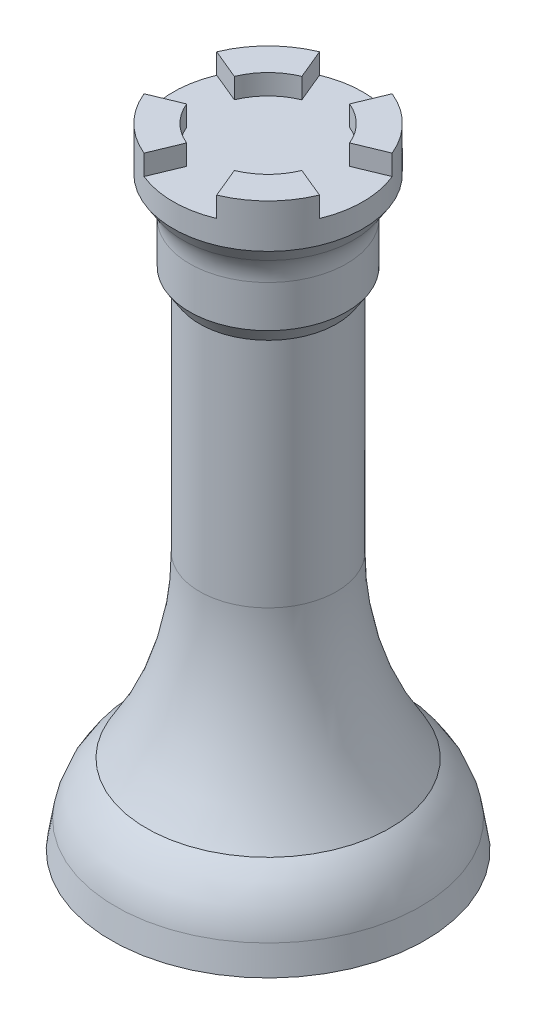
SolidWorks part; units mm, degrees
ref_plane "Front Plane" through (0, 0, 0) normal (0, 0, 1) x (1, 0, 0)
ref_plane "Top Plane" through (0, 0, 0) normal (0, 1, 0) x (1, 0, 0)
ref_plane "Right Plane" through (0, 0, 0) normal (1, 0, 0) x (0, 0, -1)
sketch "Sketch1" plane through (0, 0, 0) normal (0, 0, 1) x (1, 0, 0)
  line L21 (4.5897, -9.2849) -> (-7.0103, -9.2849)
  line L22 (-6.678, -7.2849) -> (-7.0103, -9.2849)
  line L23 (4.5897, 35.7151) -> (4.5897, -9.2849)
  line L25 (4.5897, -9.2849) -> (4.5897, 40.7151) construction
  line L26 (-1.2092, 28.0478) -> (-0.4727, 26.9092)
  line L27 (-0.0203, 35.7151) -> (4.5897, 35.7151)
  line L28 (-0.4727, 26.9092) -> (-0.4727, 9.7789)
  line L29 (-0.0203, 35.7151) -> (-0.0203, 37.2151)
  line L30 (-0.0203, 37.2151) -> (-2.4303, 37.2151)
  line L33 (-2.4303, 33.9851) -> (-1.735, 32.9104)
  line L34 (-1.2092, 31.1297) -> (-1.2092, 28.0478)
  line L36 (-2.4303, 33.9851) -> (-2.4303, 35.7151)
  line L37 (-2.4303, 37.2151) -> (-2.4303, 35.7151)
  line L38 (-0.0203, 35.7151) -> (-2.4303, 35.7151)
  arc A6 (-4.4103, -3.4011) -> (-6.678, -7.2849) centre (-0.4448, -8.3205) ccw
  arc A8 (-1.735, 32.9104) -> (-1.2092, 31.1297) centre (-4.4875, 31.1297) cw
  arc A9 (-0.4727, 9.7789) -> (-4.4103, -3.4011) centre (-24.4993, 9.7789) cw
  dimension "D6" = 11.6
  dimension "D11" = 6.3187
  dimension "D14" = 4.61
  dimension "D18" = 3.23
  dimension "D22" = 3.2783
  dimension "D2" = 2
  dimension "D3" = 1.5
  dimension "D7" = 45
  dimension "D8" = 5.8838
  dimension "D12" = 9
  dimension "D16" = 2.41
  dimension "D17" = 1.28
  dimension "D21" = 5.7989
revolve "Revolve5" add sketch "Sketch1" angle 360 about L25 region at (1.1021, 10.7577, 0) region at (-1.2253, 36.4651, 0)
revolve "Cut-Revolve1" cut sketch "Sketch1<3>" angle 45 mid plane about L25 region at (-1.2253, 36.4651, 0)
sketch "Sketch1<3>" plane through (0, 0, 0) normal (0, 0, 1) x (1, 0, 0) same geometry as "Sketch1"
pattern_circular "CirPattern1" count 4 every 90 about axis through (4.5897, -9.2849, 0) along (0, 1, 0) of "Cut-Revolve1"
sketch "Sketch2" plane through (0, -9.2849, 0) normal (0, -1, 0) x (1, 0, 0)
  circle A0 centre (4.5897, 0) radius 10
extrude "Cut-Extrude1" cut sketch "Sketch2" against normal blind 2.4 from offset 0.4 offset against normal yes
